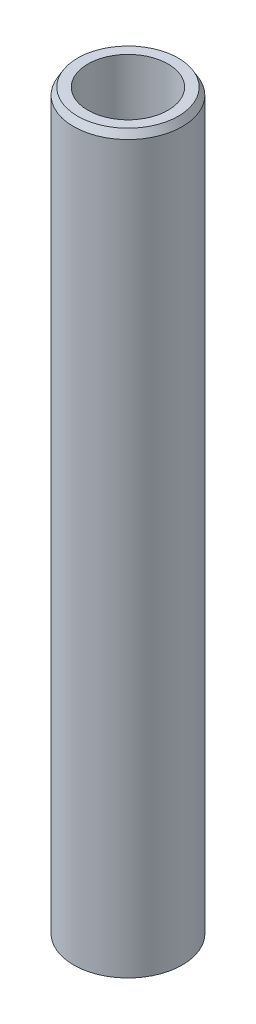
SolidWorks part; units mm, degrees
ref_plane "Front Plane" through (0, 0, 0) normal (0, 0, 1) x (1, 0, 0)
ref_plane "Top Plane" through (0, 0, 0) normal (0, 1, 0) x (1, 0, 0)
ref_plane "Right Plane" through (0, 0, 0) normal (1, 0, 0) x (0, 0, -1)
sketch "Sketch1" plane through (0, 0, 0) normal (0, 1, 0) x (1, 0, 0)
  circle A0 centre (0, 0) radius 37.5
  dimension "SHAFT_OD" = 75
extrude "Boss-Extrude1" add sketch "Sketch1" along normal blind 508.2023
sketch "Sketch2" plane through (0, 0, 0) normal (0, 1, 0) x (1, 0, 0)
  circle A0 centre (0, 0) radius 27.6466
  dimension "BORE_D" = 55.2933
extrude "Cut-Extrude1" cut sketch "Sketch2" along normal through all
chamfer "Chamfer1" distance 4.8213 angle 30 2 edges at (0, 508.2023, 37.5) (0, 0, 37.5) first distance on face at (0, 508.2023, 37.5) first distance on face at (0, 0, 27.6466)
